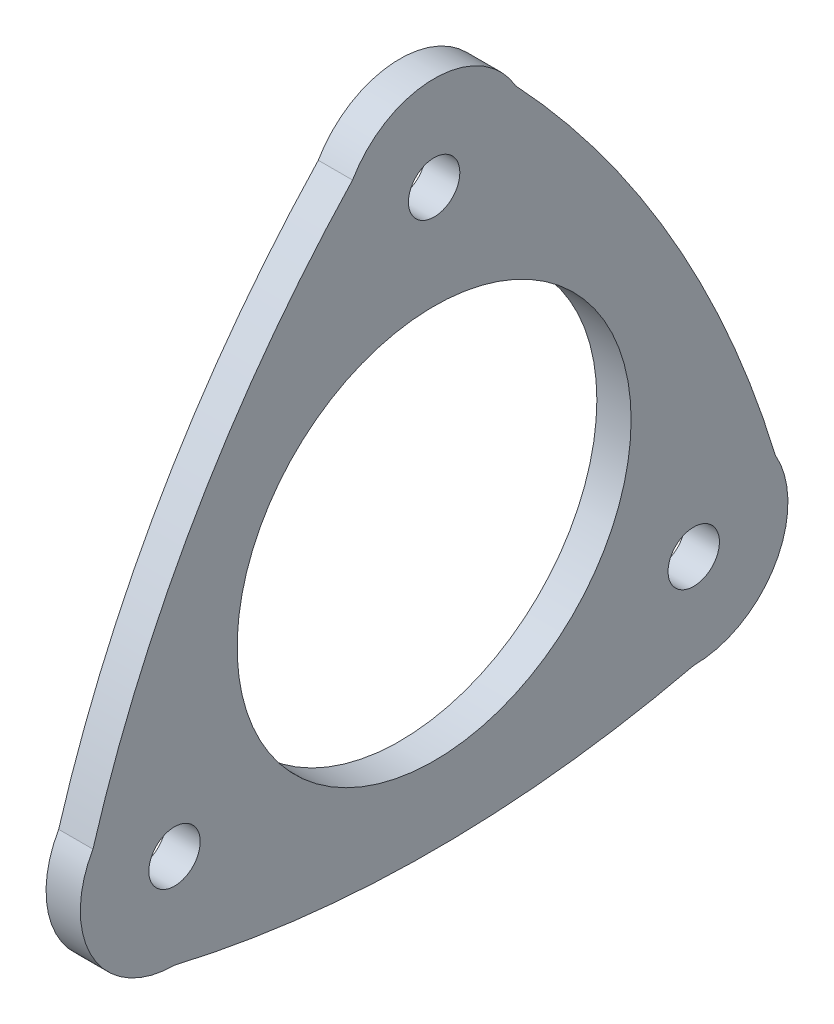
SolidWorks part; units mm, degrees
material "1023 Arkusz stali węglowej (SS)"
ref_plane "Płaszczyzna przednia" through (0, 0, 0) normal (0, 0, 1) x (1, 0, 0)
ref_plane "Płaszczyzna górna" through (0, 0, 0) normal (0, 1, 0) x (1, 0, 0)
ref_plane "Płaszczyzna prawa" through (0, 0, 0) normal (1, 0, 0) x (0, 0, -1)
sketch "Szkic1" plane through (0, 0, 0) normal (1, 0, 0) x (0, 0, -1)
  arc A0 (9.5263, 40.5) -> (-9.5263, 40.5) centre (0, 35) ccw
  arc A1 (30.3109, -28.5) -> (39.8372, -12) centre (30.3109, -17.5) ccw
  arc A2 (-39.8372, -12) -> (-30.3109, -28.5) centre (-30.3109, -17.5) ccw
  arc A3 (-30.3109, -28.5) -> (30.3109, -28.5) centre (0, 100.5489) ccw
  arc A4 (-9.5263, 40.5) -> (-39.8372, -12) centre (87.0779, -50.2745) ccw
  arc A5 (39.8372, -12) -> (9.5263, 40.5) centre (-87.0779, -50.2745) ccw
  circle A6 centre (30.3109, -17.5) radius 3
  circle A7 centre (-30.3109, -17.5) radius 3
  circle A8 centre (0, 0) radius 23
  circle A9 centre (0, 35) radius 3
  point P8 (0, 0)
  point P16 (0, 0)
  point P20 (0, 0)
  point P22 (0, 0)
  dimension "D1" = 22
  dimension "D2" = 3
  dimension "D4" = 6
  dimension "D3" = 46
extrude "Dodanie-wyciągnięcie1" add sketch "Szkic1" along normal blind 4
